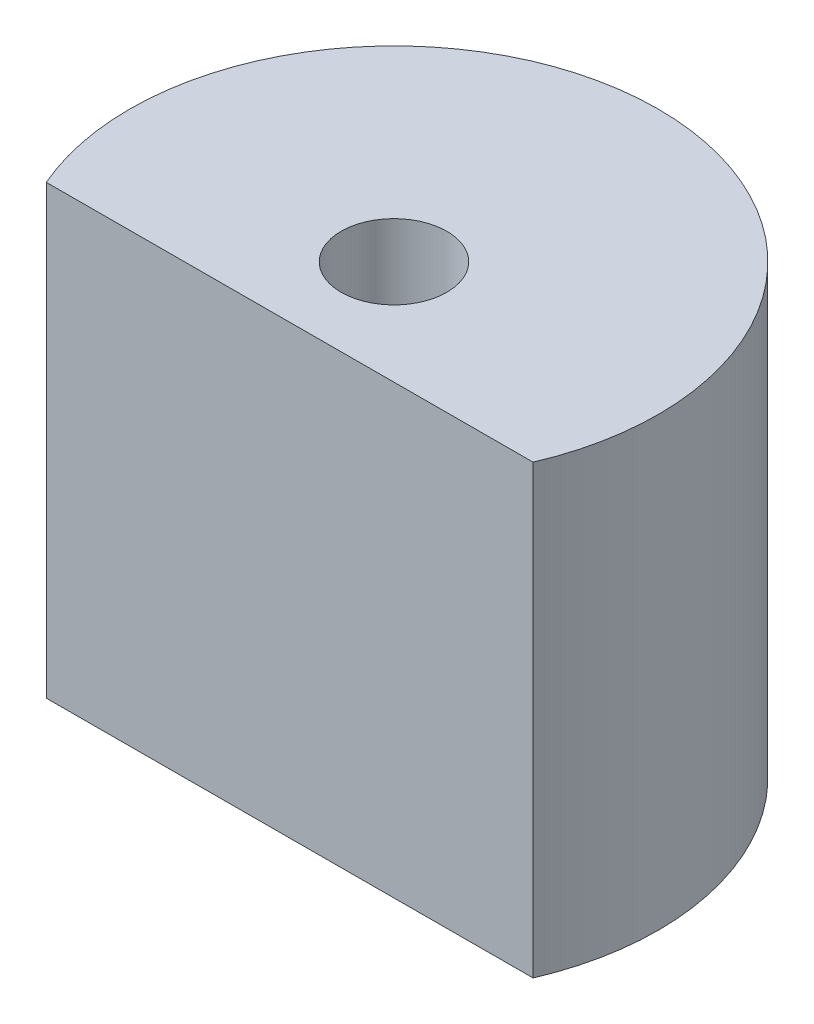
SolidWorks part; units mm, degrees
material "Oak"
ref_plane "Front" through (0, 0, 0) normal (0, 0, 1) x (1, 0, 0)
ref_plane "Top" through (0, 0, 0) normal (0, 1, 0) x (1, 0, 0)
ref_plane "Right" through (0, 0, 0) normal (1, 0, 0) x (0, 0, -1)
ref_axis "side-side" through (80.9, 0, 0) along (-1, 0, 0)
ref_axis "up-down" through (0, 50, 0) along (0, -1, 0)
ref_axis "front-back" through (0, 0, -80.9) along (0, 0, 1)
sketch "Sketch1" plane through (0, 0, 0) normal (0, 1, 0) x (1, 0, 0)
  circle A0 centre (0, 0) radius 7.9375
  circle A1 centre (0, 0) radius 1.5875
  dimension "D1" = 3.175
  dimension "D2" = 15.875
extrude "Boss-Extrude1" add sketch "Sketch1" along normal blind 13.4112
sketch "Sketch2" plane through (0, 0, 0) normal (0, -1, 0) x (1, 0, 0)
  line L0 (7.2983, 3.1206) -> (-7.2841, 3.1536) construction
  line L1 (12.5818, 3.1086) -> (-13.0726, 3.1667)
  point P2 (12.5818, 3.1536)
  point P4 (-13.0726, 3.1086)
extrude "Cut-Extrude1" cut sketch "Sketch2" against normal through all both and the other way through all flip side to cut
